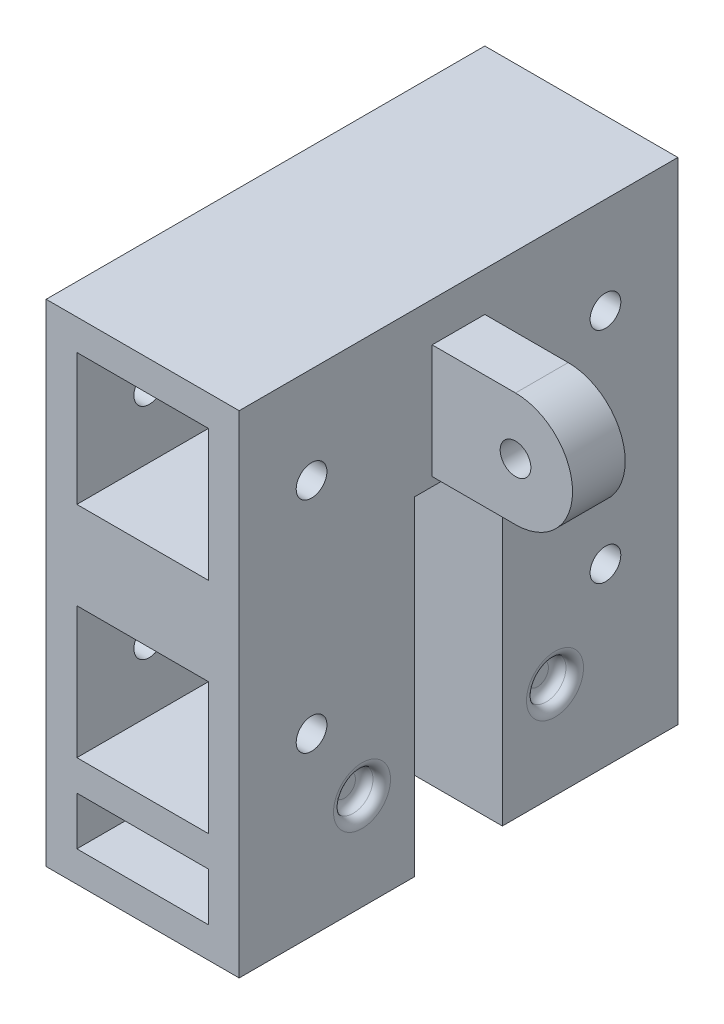
SolidWorks part; units mm, degrees
ref_plane "Front Plane" through (0, 0, 0) normal (0, 0, 1) x (1, 0, 0)
ref_plane "Top Plane" through (0, 0, 0) normal (0, 1, 0) x (1, 0, 0)
ref_plane "Right Plane" through (0, 0, 0) normal (1, 0, 0) x (0, 0, -1)
sketch "Sketch1" plane through (0, 0, 0) normal (0, 0, 1) x (1, 0, 0)
  line L1 (-25.0962, 42.3339) -> (-3.0962, 42.3339)
  line L2 (-25.0962, 42.3339) -> (-25.0962, -13.6661)
  line L3 (-25.0962, -13.6661) -> (-3.0962, -13.6661)
  line L4 (-3.0962, 42.3339) -> (-3.0962, -13.6661)
  line L5 (-21.5962, 38.8339) -> (-6.5962, 38.8339)
  line L6 (-21.5962, 38.8339) -> (-21.5962, 23.8339)
  line L7 (-21.5962, 23.8339) -> (-6.5962, 23.8339)
  line L8 (-6.5962, 38.8339) -> (-6.5962, 23.8339)
  dimension "D1" = 22
  dimension "D2" = 56
  dimension "D3" = 15
  dimension "D4" = 3.5
  dimension "D5" = 3.5
  dimension "D6" = 15
extrude "Boss-Extrude1" add sketch "Sketch1" along normal blind 20
sketch "Sketch2" plane through (0, 0, 20) normal (0, 0, 1) x (1, 0, 0)
  line L0 (-3.0962, -13.6661) -> (-3.0962, 42.3339) construction
  line L1 (-21.5962, 13.8339) -> (-6.5962, 13.8339)
  line L2 (-21.5962, 13.8339) -> (-21.5962, -1.1661)
  line L3 (-21.5962, -1.1661) -> (-6.5962, -1.1661)
  line L4 (-6.5962, 13.8339) -> (-6.5962, -1.1661)
  line L5 (-21.5962, 23.8339) -> (-6.5962, 23.8339) construction
  line L6 (-25.0962, -13.6661) -> (-3.0962, -13.6661) construction
  line L7 (-21.5962, -4.6661) -> (-6.5962, -4.6661)
  line L8 (-21.5962, -4.6661) -> (-21.5962, -10.1661)
  line L9 (-21.5962, -10.1661) -> (-6.5962, -10.1661)
  line L10 (-6.5962, -4.6661) -> (-6.5962, -10.1661)
  dimension "D1" = 15
  dimension "D2" = 3.5
  dimension "D3" = 10
  dimension "D4" = 15
  dimension "D5" = 15
  dimension "D6" = 3.5
  dimension "D7" = 3.5
extrude "Cut-Extrude1" cut sketch "Sketch2" against normal offset from surface (15.5 mm away) 4.5 up to face at (-14.0962, 14.3339, 0)
sketch "Sketch3" plane through (-25.0962, 0, 0) normal (-1, 0, 0) x (0, 0, 1)
  line L0 (11.75, -13.6661) -> (11.75, 43.4795) construction
  line L1 (20, -13.6661) -> (0, -13.6661) construction
  line L3 (20, 38.8339) -> (0, 38.8339) construction
  line L4 (4.5, 13.8339) -> (20, 13.8339) construction
  line L5 (20, 42.3339) -> (20, -13.6661) construction
  circle A0 centre (11.75, 31.3339) radius 1.75
  circle A1 centre (11.75, 6.3339) radius 1.75
  dimension "D2" = 3.5
  dimension "D3" = 7.5
  dimension "D4" = 7.5
  dimension "D1" = 8.25
extrude "Cut-Extrude2" cut sketch "Sketch3" against normal blind 35
ref_plane "Plane1" through (0, 0, -5) normal (0, 0, -1) x (-1, 0, 0)
mirror "Mirror3" about plane through (0, 0, -5) normal (0, 0, -1) of bodies 104
sketch "Sketch4" plane through (0, 0, 0) normal (0, 0, -1) x (-1, 0, 0)
  line L0 (6.5962, 38.8339) -> (21.5962, 38.8339) construction
  line L1 (6.5962, 23.8339) -> (6.5962, 38.8339) construction
  line L3 (21.5962, 38.8339) -> (21.5962, 23.8339) construction
  line L4 (6.5962, 38.8339) -> (21.5962, 38.8339)
  line L5 (6.5962, 23.8339) -> (6.5962, 38.8339)
  line L7 (21.5962, 38.8339) -> (21.5962, 23.8339)
  line L8 (3.0962, 42.3339) -> (25.0962, 42.3339) construction
  line L9 (3.0962, 42.3339) -> (25.0962, 42.3339)
  line L10 (3.0962, 42.3339) -> (3.0962, 23.8339)
  line L11 (3.0962, -13.6661) -> (3.0962, 42.3339) construction
  line L12 (3.0962, 23.8339) -> (6.5962, 23.8339)
  line L13 (25.0962, 42.3339) -> (25.0962, -13.6661) construction
  line L14 (25.0962, 23.8339) -> (25.0962, 42.3339)
  line L15 (21.5962, 23.8339) -> (25.0962, 23.8339)
extrude "Boss-Extrude2" add sketch "Sketch4" along normal up to surface (10 mm away) up to face at (-14.0962, 14.3339, -10)
sketch "Sketch6" plane through (0, 0, -5) normal (0, 0, -1) x (-1, 0, 0)
  line L0 (6.5962, 31.3339) -> (-6.4038, 31.3339) construction
  line L1 (6.5962, 23.8339) -> (6.5962, 38.8339) construction
  line L2 (-6.4038, 37.8339) -> (3.0962, 37.8339)
  line L3 (3.0962, -13.6661) -> (3.0962, 42.3339) construction
  line L4 (3.0962, 37.8339) -> (3.0962, 24.8339)
  line L5 (3.0962, 24.8339) -> (-6.4038, 24.8339)
  circle A0 centre (-6.4038, 31.3339) radius 1.75
  arc A1 (-6.4038, 37.8339) -> (-6.4038, 24.8339) centre (-6.4038, 31.3339) ccw
  dimension "D1" = 3.5
  dimension "D2" = 13
  dimension "D3" = 13
extrude "Boss-Extrude3" add sketch "Sketch6" along normal blind 3 and the other way blind 3
sketch "Sketch7" plane through (-3.0962, 0, 0) normal (1, 0, 0) x (0, 0, -1)
  line L0 (-20, -2.6661) -> (30, -2.6661) construction
  line L1 (-20, -13.6661) -> (-20, 42.3339) construction
  line L2 (30, -13.6661) -> (30, 42.3339) construction
  line L3 (30, -13.6661) -> (10, -13.6661) construction
  line L4 (10, -13.6661) -> (10, 23.8339) construction
  line L5 (0, -13.6661) -> (0, 23.8339) construction
  circle A0 centre (16, -2.6661) radius 2.25
  circle A1 centre (-6, -2.6661) radius 2.25
  dimension "D2" = 6
  dimension "D3" = 6
  dimension "D4" = 4.5
  dimension "D1" = 11
extrude "Cut-Extrude3" cut sketch "Sketch7" against normal blind 2
fillet "Fillet1" radius 1 4 edges at (-5.0962, -0.4161, -16) (-5.0962, -0.4161, 6) (-3.0962, -0.4161, 6) (-3.0962, -0.4161, -16)
